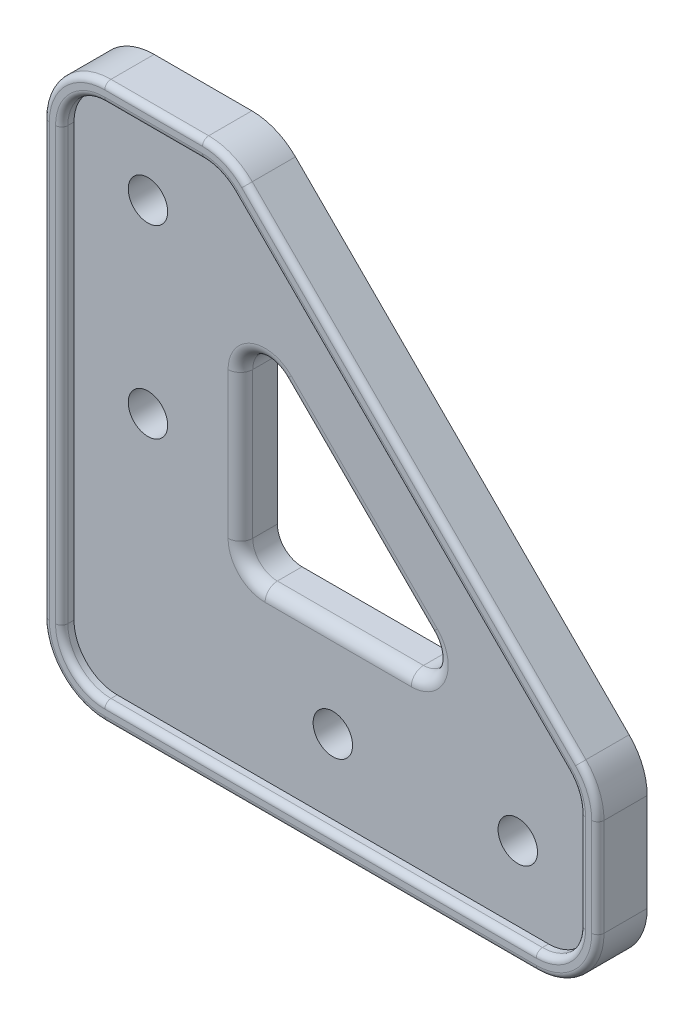
SolidWorks part; units mm, degrees
ref_plane "Front Plane" through (0, 0, 0) normal (0, 0, 1) x (1, 0, 0)
ref_plane "Top Plane" through (0, 0, 0) normal (0, 1, 0) x (1, 0, 0)
ref_plane "Right Plane" through (0, 0, 0) normal (1, 0, 0) x (0, 0, -1)
sketch "Sketch1" plane through (0, 0, 0) normal (0, 0, 1) x (1, 0, 0)
  line L0 (16.4645, 43.5355) -> (43.5355, 16.4645)
  line L1 (5, 0) -> (40, 0)
  line L2 (0, 5) -> (0, 40)
  line L3 (5, 45) -> (12.9289, 45)
  line L4 (45, 5) -> (45, 12.9289)
  arc A0 (0, 5) -> (5, 0) centre (5, 5) ccw
  arc A1 (45, 5) -> (40, 0) centre (40, 5) cw
  arc A2 (45, 12.9289) -> (43.5355, 16.4645) centre (40, 12.9289) ccw
  arc A3 (16.4645, 43.5355) -> (12.9289, 45) centre (12.9289, 40) ccw
  arc A4 (5, 45) -> (0, 40) centre (5, 40) ccw
  point P8 (0, 0)
  point P11 (45, 0)
  point P14 (45, 15)
  point P19 (0, 45)
  dimension "D4" = 5
  dimension "D1" = 45
  dimension "D2" = 45
  dimension "D3" = 15
extrude "Boss-Extrude1" add sketch "Sketch1" along normal blind 3
sketch "Sketch2" plane through (0, 0, 3) normal (0, 0, 1) x (1, 0, 0)
  line L0 (7.5, 7.5) -> (58.6399, 7.5) construction
  line L2 (55, 0) -> (-55, 0) construction
  line L4 (7.5, 40) -> (7.5, 5)
  line L5 (7.5, 40) -> (7.5, 7.5) construction
  circle A0 centre (7.5, 37.5) radius 1.6
  circle A2 centre (7.5, 22.5) radius 1.6
  circle A3 centre (22.5, 7.5) radius 1.6
  circle A4 centre (37.5, 7.5) radius 1.6
  dimension "D7" = 3.2
  dimension "D1" = 7.5
  dimension "D2" = 7.5
  dimension "D3" = 15
  dimension "D4" = 15
  dimension "D5" = 15
  dimension "D6" = 15
extrude "Cut-Extrude1" cut sketch "Sketch2" against normal through all
sketch "Sketch3" plane through (0, 0, 3) normal (0, 0, 1) x (1, 0, 0)
  line L5 (5, 1.5) -> (40, 1.5)
  line L6 (43.5, 5) -> (43.5, 12.9289)
  line L7 (42.4749, 15.4038) -> (15.4038, 42.4749)
  line L8 (12.9289, 43.5) -> (5, 43.5)
  line L9 (1.5, 40) -> (1.5, 5)
  line L10 (5, 0) -> (40, 0)
  line L11 (45, 5) -> (45, 12.9289)
  line L12 (43.5355, 16.4645) -> (16.4645, 43.5355)
  line L13 (12.9289, 45) -> (5, 45)
  line L14 (0, 40) -> (0, 5)
  line L15 (5, 0) -> (40, 0)
  line L16 (45, 5) -> (45, 12.9289)
  line L17 (43.5355, 16.4645) -> (16.4645, 43.5355)
  line L18 (12.9289, 45) -> (5, 45)
  line L19 (0, 40) -> (0, 5)
  arc A5 (40, 1.5) -> (43.5, 5) centre (40, 5) ccw
  arc A6 (43.5, 12.9289) -> (42.4749, 15.4038) centre (40, 12.9289) ccw
  arc A7 (15.4038, 42.4749) -> (12.9289, 43.5) centre (12.9289, 40) ccw
  arc A8 (5, 43.5) -> (1.5, 40) centre (5, 40) ccw
  arc A9 (1.5, 5) -> (5, 1.5) centre (5, 5) ccw
  arc A10 (0, 5) -> (5, 0) centre (5, 5) ccw
  arc A11 (40, 0) -> (45, 5) centre (40, 5) ccw
  arc A12 (45, 12.9289) -> (43.5355, 16.4645) centre (40, 12.9289) ccw
  arc A13 (16.4645, 43.5355) -> (12.9289, 45) centre (12.9289, 40) ccw
  arc A14 (5, 45) -> (0, 40) centre (5, 40) ccw
  arc A15 (0, 5) -> (5, 0) centre (5, 5) ccw
  arc A16 (40, 0) -> (45, 5) centre (40, 5) ccw
  arc A17 (45, 12.9289) -> (43.5355, 16.4645) centre (40, 12.9289) ccw
  arc A18 (16.4645, 43.5355) -> (12.9289, 45) centre (12.9289, 40) ccw
  arc A19 (5, 45) -> (0, 40) centre (5, 40) ccw
  dimension "D2" = 1.5
  dimension "D1" = 0
extrude "Boss-Extrude2" add sketch "Sketch3" along normal blind 1
fillet "Fillet1" radius 0.5 20 edges at (42.4749, 2.5251, 4) (43.5, 8.9645, 4) (43.2336, 14.2683, 4) (28.9393, 28.9393, 4) (14.2683, 43.2336, 4) (8.9645, 43.5, 4) (2.5251, 42.4749, 4) (1.5, 22.5, 4) (2.5251, 2.5251, 4) (22.5, 1.5, 4) (0, 22.5, 4) (1.4645, 43.5355, 4) (8.9645, 45, 4) (14.8423, 44.6194, 4) (30, 30, 4) (44.6194, 14.8423, 4) (45, 8.9645, 4) (43.5355, 1.4645, 4) (22.5, 0, 4) (1.4645, 1.4645, 4)
sketch "Sketch4" plane through (0, 0, 3) normal (0, 0, 1) x (1, 0, 0)
  line L0 (15, 28.8579) -> (15, 17)
  line L1 (17, 15) -> (28.8579, 15)
  line L2 (18.4142, 30.2721) -> (30.2721, 18.4142)
  line L3 (-702.1068, -702.1068) -> (34653.2323, 34653.2323) construction
  line L5 (40, 0) -> (5, 0) construction
  line L6 (16.4645, 43.5355) -> (43.5355, 16.4645) construction
  line L8 (0, 40) -> (0, 5) construction
  line L9 (16.4645, 43.5355) -> (43.5355, 16.4645) construction
  arc A0 (17, 15) -> (15, 17) centre (17, 17) cw
  arc A1 (18.4142, 30.2721) -> (15, 28.8579) centre (17, 28.8579) ccw
  arc A2 (30.2721, 18.4142) -> (28.8579, 15) centre (28.8579, 17) cw
  point P14 (15, 15)
  point P17 (15, 33.6863)
  point P20 (33.6863, 15)
  dimension "D5" = 2
  dimension "D6" = 2
  dimension "D7" = 2
  dimension "D1" = 8
  dimension "D2" = 15
  dimension "D3" = 15
  dimension "D4" = 8
extrude "Cut-Extrude2" cut sketch "Sketch4" against normal through all
fillet "Fillet2" radius 1 6 edges at (15.5858, 15.5858, 3) (22.9289, 15, 3) (30.7056, 16.2346, 3) (24.3431, 24.3431, 3) (16.2346, 30.7056, 3) (15, 22.9289, 3)
